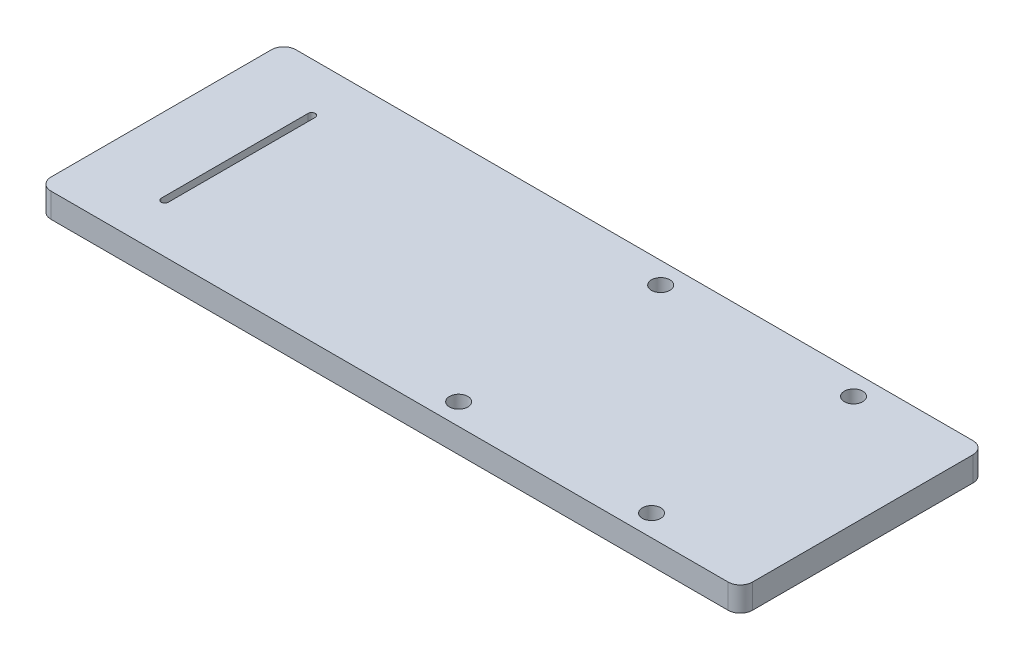
SolidWorks part; units mm, degrees
material "6061 Alloy"
ref_plane "Front Plane" through (0, 0, 0) normal (0, 0, 1) x (1, 0, 0)
ref_plane "Top Plane" through (0, 0, 0) normal (0, 1, 0) x (1, 0, 0)
ref_plane "Right Plane" through (0, 0, 0) normal (1, 0, 0) x (0, 0, -1)
sketch "Sketch1" plane through (0, 0, 0) normal (0, 1, 0) x (1, 0, 0)
  line L1 (-181.9, -63.5) -> (181.9, -63.5)
  line L2 (-181.9, -63.5) -> (-181.9, 63.5)
  line L3 (-181.9, 63.5) -> (181.9, 63.5)
  line L4 (181.9, -63.5) -> (181.9, 63.5)
  line L5 (-181.9, -63.5) -> (181.9, 63.5) construction
  line L6 (-181.9, 63.5) -> (181.9, -63.5) construction
  point P0 (0, 0)
  dimension "D1" = 127
  dimension "D2" = 363.8
extrude "Boss-Extrude1" add sketch "Sketch1" along normal blind 12.7
fillet "Fillet1" radius 6.35 4 edges at (-181.9, 6.35, -63.5) (181.9, 6.35, -63.5) (181.9, 6.35, 63.5) (-181.9, 6.35, 63.5)
sketch "Sketch2" plane through (0, 12.7, 0) normal (0, 1, 0) x (1, 0, 0)
  line L0 (-181.9, 0) -> (181.9, 0) construction
  line L3 (-181.9, 57.15) -> (-181.9, -57.15) construction
  line L4 (181.9, -57.15) -> (181.9, 57.15) construction
  line L5 (0, 63.5) -> (0, -63.5) construction
  line L6 (175.55, 63.5) -> (-175.55, 63.5) construction
  line L7 (-175.55, -63.5) -> (175.55, -63.5) construction
  circle A0 centre (24.73, 52.3748) radius 4.7752
  circle A1 centre (24.73, -52.3748) radius 4.7752
  circle A2 centre (124.75, -52.3748) radius 4.7752
  circle A3 centre (124.75, 52.3748) radius 4.7752
  point P14 (24.73, 57.15)
  dimension "D1" = 100.02
  dimension "D4" = 9.5504
  dimension "D2" = 6.35
  dimension "D3" = 57.15
  dimension "D5" = 57.15
extrude "Cut-Extrude1" cut sketch "Sketch2" against normal through all
sketch "Sketch3" plane through (0, 0, 0) normal (0, -1, 0) x (1, 0, 0)
  line L0 (-141.9753, 38.1) -> (-141.9753, -38.1) construction
  line L2 (-140.1464, 38.1) -> (-140.1464, -38.1)
  line L3 (-143.8041, 38.1) -> (-143.8041, -38.1)
  line L4 (-181.9, 0) -> (181.9, 0) construction
  line L5 (-181.9, -57.15) -> (-181.9, 57.15) construction
  line L6 (181.9, 57.15) -> (181.9, -57.15) construction
  arc A0 (-140.1464, 38.1) -> (-143.8041, 38.1) centre (-141.9753, 38.1) ccw
  arc A1 (-143.8041, -38.1) -> (-140.1464, -38.1) centre (-141.9753, -38.1) ccw
  point P4 (-141.9753, 0)
  dimension "D1" = 0
  dimension "D2" = 76.2
extrude "Cut-Extrude2" cut sketch "Sketch3" against normal up to next
